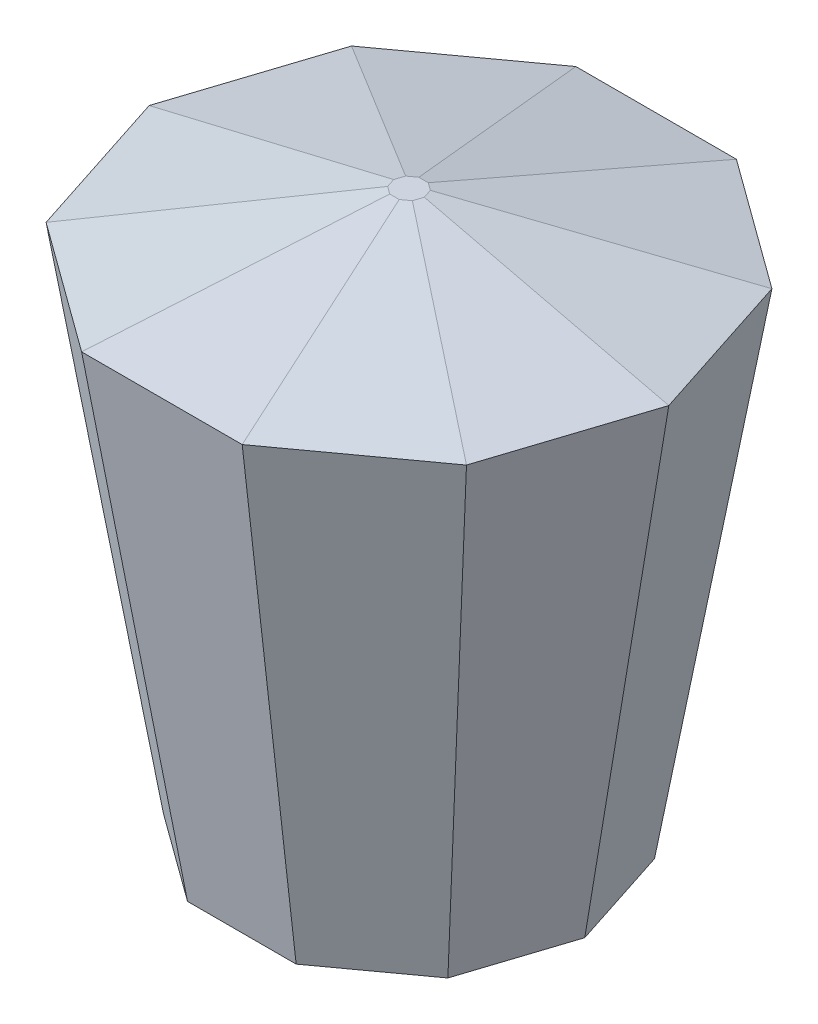
SolidWorks part; units mm, degrees
ref_plane "Front Plane" through (0, 0, 0) normal (0, 0, 1) x (1, 0, 0)
ref_plane "Top Plane" through (0, 0, 0) normal (0, 1, 0) x (1, 0, 0)
ref_plane "Right Plane" through (0, 0, 0) normal (1, 0, 0) x (0, 0, -1)
sketch "Croquis1" plane through (0, 0, 0) normal (0, 1, 0) x (1, 0, 0)
  line L0 (4.8912, 3.5537) -> (1.8683, 5.75)
  line L1 (-6.0459, 0) -> (-4.8912, -3.5537)
  line L2 (-4.8912, -3.5537) -> (-1.8683, -5.75)
  line L3 (-1.8683, -5.75) -> (1.8683, -5.75)
  line L4 (1.8683, -5.75) -> (4.8912, -3.5537)
  line L5 (4.8912, -3.5537) -> (6.0459, 0)
  line L6 (6.0459, 0) -> (4.8912, 3.5537)
  line L7 (1.8683, 5.75) -> (-1.8683, 5.75)
  line L8 (-1.8683, 5.75) -> (-4.8912, 3.5537)
  line L9 (-4.8912, 3.5537) -> (-6.0459, 0)
  circle A0 centre (0, 0) radius 5.75 construction
  dimension "D1" = 11.5
ref_plane "Plano1" through (0, 17.3, 0) normal (0, 1, 0) x (1, 0, 0)
ref_plane "Plano2" through (0, 19.3, 0) normal (0, 1, 0) x (1, 0, 0)
sketch "Croquis2" plane through (0, 17.3, 0) normal (0, 1, 0) x (1, 0, 0)
  line L1 (-8.9374, 0) -> (-7.2305, -5.2533)
  line L2 (-7.2305, -5.2533) -> (-2.7618, -8.5)
  line L3 (-2.7618, -8.5) -> (2.7618, -8.5)
  line L4 (2.7618, -8.5) -> (7.2305, -5.2533)
  line L5 (7.2305, -5.2533) -> (8.9374, 0)
  line L6 (8.9374, 0) -> (7.2305, 5.2533)
  line L7 (7.2305, 5.2533) -> (2.7618, 8.5)
  line L8 (2.7618, 8.5) -> (-2.7618, 8.5)
  line L9 (-2.7618, 8.5) -> (-7.2305, 5.2533)
  line L10 (-7.2305, 5.2533) -> (-8.9374, 0)
  circle A0 centre (0, 0) radius 8.5 construction
  dimension "D1" = 17
sketch "Croquis4" plane through (0, 19.3, 0) normal (0, 1, 0) x (1, 0, 0)
  line L1 (-0.5257, 0) -> (-0.4253, -0.309)
  line L2 (-0.4253, -0.309) -> (-0.1625, -0.5)
  line L3 (-0.1625, -0.5) -> (0.1625, -0.5)
  line L4 (0.1625, -0.5) -> (0.4253, -0.309)
  line L5 (0.4253, -0.309) -> (0.5257, 0)
  line L6 (0.5257, 0) -> (0.4253, 0.309)
  line L7 (0.4253, 0.309) -> (0.1625, 0.5)
  line L8 (0.1625, 0.5) -> (-0.1625, 0.5)
  line L9 (-0.1625, 0.5) -> (-0.4253, 0.309)
  line L10 (-0.4253, 0.309) -> (-0.5257, 0)
  circle A0 centre (0, 0) radius 0.5 construction
  dimension "D1" = 1
loft "Recubrir1" add profiles "Croquis1", "Croquis2" start constraint default connector at (-6.0459, 0, 0) connector at (-8.9374, 17.3, 0)
loft "Recubrir2" add profiles "Croquis4", "Croquis2<3>" connector at (-0.1625, 19.3, -0.5) connector at (-2.7618, 17.3, -8.5)
sketch "Croquis2<3>" plane through (0, 17.3, 0) normal (0, 1, 0) x (1, 0, 0) same geometry as "Croquis2"
sketch "Croquis5" plane through (0, 0, 0) normal (0, -1, 0) x (1, 0, 0)
  circle A0 centre (0, 0) radius 1.5
  point P3 (0, 0)
  dimension "D1" = 3
extrude "Cortar-Extruir1" cut sketch "Croquis5" against normal blind 18
